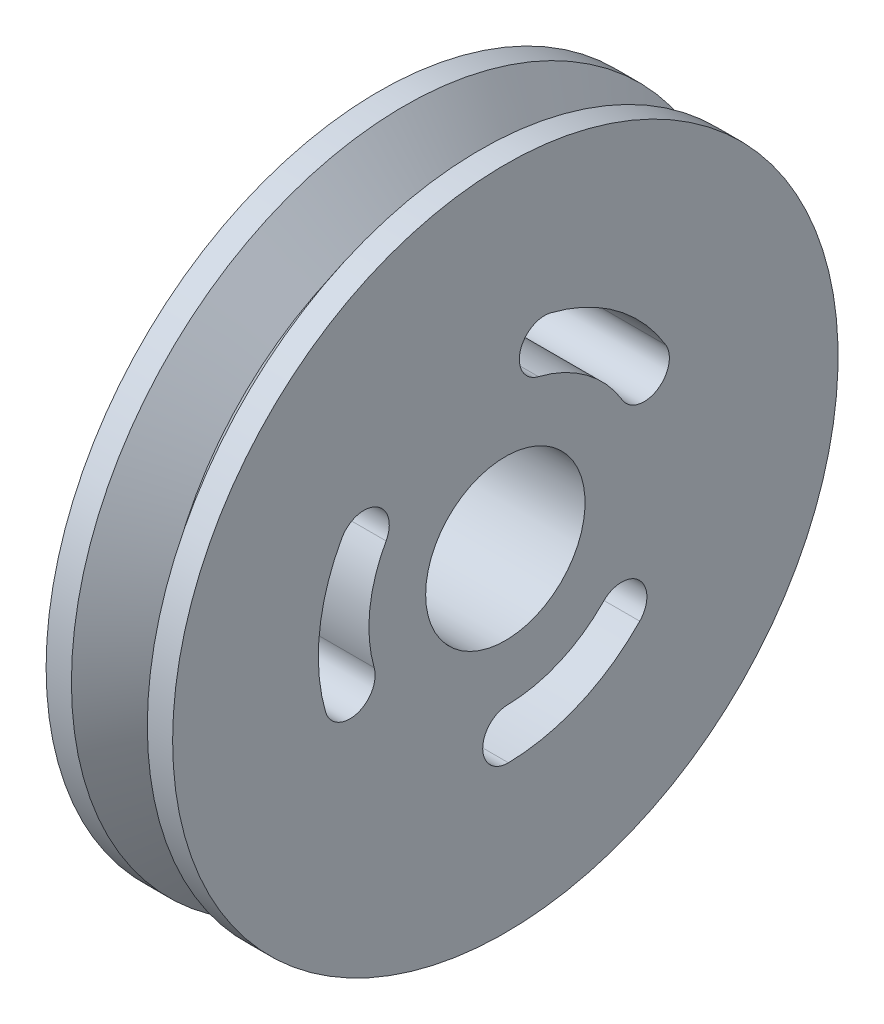
SolidWorks part; units mm, degrees
ref_plane "Front Plane" through (0, 0, 0) normal (0, 0, 1) x (1, 0, 0)
ref_plane "Top Plane" through (0, 0, 0) normal (0, 1, 0) x (1, 0, 0)
ref_plane "Right Plane" through (0, 0, 0) normal (1, 0, 0) x (0, 0, -1)
sketch "Sketch1" plane through (0, 0, 0) normal (0, 0, 1) x (1, 0, 0)
  line L0 (0, 0) -> (16.5774, 0) construction
  line L1 (1.27, 16.7) -> (3.175, 14.16)
  line L2 (0, 4) -> (6.35, 4)
  line L3 (0, 4) -> (0, 16.7)
  line L4 (0, 16.7) -> (1.27, 16.7)
  line L5 (6.35, 4) -> (6.35, 16.7)
  line L6 (3.175, 14.16) -> (5.08, 16.7)
  line L7 (3.175, 14.16) -> (3.175, 4) construction
  line L8 (5.08, 16.7) -> (6.35, 16.7)
  dimension "D1" = 8
  dimension "D2" = 12.7
  dimension "D3" = 6.35
  dimension "D4" = 1.27
  dimension "D5" = 2.54
revolve "Revolve1" add sketch "Sketch1" angle 360 about L0
sketch "Sketch2" plane through (0, 0, 0) normal (-1, 0, 0) x (0, 0, 1)
  arc A0 (-4.921, -4.7615) -> (-6.7463, -6.5278) centre (-5.8337, -5.6447) ccw construction
  arc A1 (-4.921, -4.7615) -> (-0.1127, -6.8466) centre (0, 0) ccw construction
  arc A2 (-0.1546, -9.3862) -> (-0.1127, -6.8466) centre (-0.1336, -8.1164) ccw construction
  arc A3 (-6.7463, -6.5278) -> (-0.1546, -9.3862) centre (0, 0) ccw construction
  arc A4 (-4.921, -4.7615) -> (-6.7463, -6.5278) centre (-5.8337, -5.6447) ccw
  arc A5 (-4.921, -4.7615) -> (-0.1127, -6.8466) centre (0, 0) ccw
  arc A6 (-0.1546, -9.3862) -> (-0.1127, -6.8466) centre (-0.1336, -8.1164) ccw
  arc A7 (-6.7463, -6.5278) -> (-0.1546, -9.3862) centre (0, 0) ccw
  arc A8 (-1.6631, 6.6425) -> (-2.28, 9.1064) centre (-1.9716, 7.8744) ccw
  arc A9 (-2.28, 9.1064) -> (-8.0514, 4.827) centre (0, 0) ccw
  arc A10 (-8.0514, 4.827) -> (-5.8729, 3.5209) centre (-6.9622, 4.1739) ccw
  arc A11 (-1.6631, 6.6425) -> (-5.8729, 3.5209) centre (0, 0) ccw
  arc A12 (6.5841, -1.8809) -> (9.0264, -2.5786) centre (7.8052, -2.2298) ccw
  arc A13 (9.0264, -2.5786) -> (8.206, 4.5593) centre (0, 0) ccw
  arc A14 (8.206, 4.5593) -> (5.9857, 3.3257) centre (7.0958, 3.9425) ccw
  arc A15 (6.5841, -1.8809) -> (5.9857, 3.3257) centre (0, 0) ccw
  point P21 (0, 0)
  dimension "D1" = 3
extrude "Cut-Extrude1" cut sketch "Sketch2" against normal through all both and the other way through all
